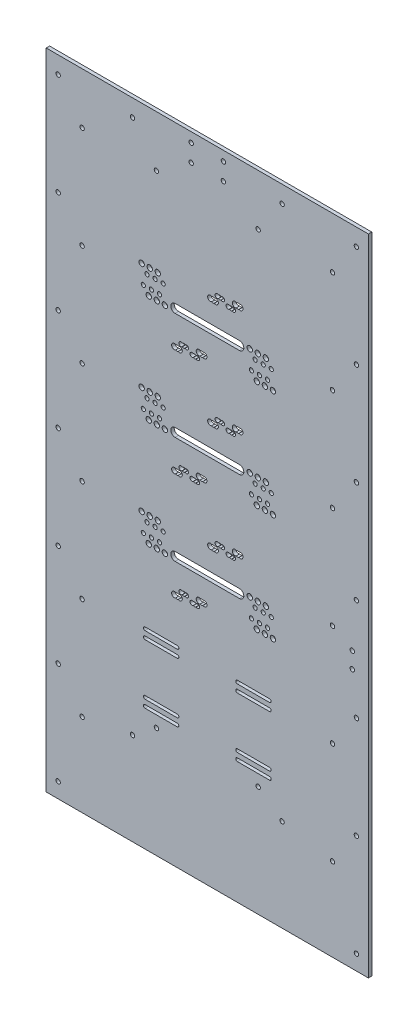
SolidWorks part; units mm, degrees
ref_plane "Front Plane" through (0, 0, 0) normal (0, 0, 1) x (1, 0, 0)
ref_plane "Top Plane" through (0, 0, 0) normal (0, 1, 0) x (1, 0, 0)
ref_plane "Right Plane" through (0, 0, 0) normal (1, 0, 0) x (0, 0, -1)
sketch "Sketch1" plane through (0, 0, 0) normal (0, 0, 1) x (1, 0, 0)
  line L1 (-165.9868, 403.6022) -> (134.0132, 403.6022)
  line L2 (-165.9868, 403.6022) -> (-165.9868, -196.3978)
  line L3 (-165.9868, -196.3978) -> (134.0132, -196.3978)
  line L4 (134.0132, 403.6022) -> (134.0132, -196.3978)
  dimension "D1" = 600
  dimension "D2" = 300
extrude "Boss-Extrude1" add sketch "Sketch1" along normal blind 3.175
sketch "Sketch2" plane through (0, 0, 0) normal (0, 0, -1) x (-1, 0, 0)
  line L0 (15.9868, -196.3978) -> (15.9868, 403.6022) construction
  line L1 (165.9868, -196.3978) -> (-134.0132, -196.3978) construction
  line L2 (-134.0132, 403.6022) -> (165.9868, 403.6022) construction
  line L3 (0.9868, 53.6022) -> (30.9868, 53.6022) construction
  line L4 (0.9868, 153.6022) -> (30.9868, 153.6022) construction
  line L5 (0.9868, 253.6022) -> (30.9868, 253.6022) construction
  point P8 (15.9868, 53.6022)
  point P11 (15.9868, 153.6022)
  dimension "D1" = 30
  dimension "D2" = 30
  dimension "D3" = 100
  dimension "D4" = 100
  dimension "D5" = 250
sketch "Sketch4" plane through (0, 0, 3.175) normal (0, 0, 1) x (1, 0, 0)
  line L0 (-45.9868, 253.6022) -> (14.0132, 253.6022) construction
  line L1 (-45.9868, 257.6022) -> (14.0132, 257.6022)
  line L2 (-45.9868, 249.6022) -> (14.0132, 249.6022)
  line L3 (-15.9868, -196.3978) -> (-15.9868, 403.6022) construction
  line L4 (-0.9868, 253.6022) -> (-30.9868, 253.6022) construction
  line L5 (-45.9868, 153.6022) -> (14.0132, 153.6022) construction
  line L6 (-45.9868, 157.6022) -> (14.0132, 157.6022)
  line L7 (-45.9868, 149.6022) -> (14.0132, 149.6022)
  line L8 (-45.9868, 53.6022) -> (14.0132, 53.6022) construction
  line L9 (-45.9868, 57.6022) -> (14.0132, 57.6022)
  line L10 (-45.9868, 49.6022) -> (14.0132, 49.6022)
  line L11 (-0.9868, 53.6022) -> (-30.9868, 53.6022) construction
  line L12 (-0.9868, 153.6022) -> (-30.9868, 153.6022) construction
  arc A0 (-45.9868, 257.6022) -> (-45.9868, 249.6022) centre (-45.9868, 253.6022) ccw
  arc A1 (14.0132, 249.6022) -> (14.0132, 257.6022) centre (14.0132, 253.6022) ccw
  arc A2 (-45.9868, 157.6022) -> (-45.9868, 149.6022) centre (-45.9868, 153.6022) ccw
  arc A3 (14.0132, 149.6022) -> (14.0132, 157.6022) centre (14.0132, 153.6022) ccw
  arc A4 (-45.9868, 57.6022) -> (-45.9868, 49.6022) centre (-45.9868, 53.6022) ccw
  arc A5 (14.0132, 49.6022) -> (14.0132, 57.6022) centre (14.0132, 53.6022) ccw
  point P2 (-15.9868, 253.6022)
  point P14 (-15.9868, 153.6022)
  point P21 (-15.9868, 53.6022)
  dimension "D1" = 15
  dimension "D2" = 8
  dimension "D3" = 15
  dimension "D4" = 8
  dimension "D5" = 15
  dimension "D6" = 8
extrude "Cut-Extrude1" cut sketch "Sketch4" against normal blind 10
sketch "Sketch5" plane through (0, 0, 0) normal (0, 0, -1) x (-1, 0, 0)
  line L0 (45.9868, 149.6022) -> (-14.0132, 149.6022) construction
  arc A27 (-11.0351, 86.887) -> (-13.5351, 86.887) centre (-12.2851, 84.722) ccw
  circle A34 centre (-30.1263, 32.8202) radius 2.5
  circle A35 centre (-37.6263, 32.8202) radius 2.5
  circle A36 centre (-45.1263, 32.8202) radius 2.5
  arc A37 (20.0603, 26.9076) -> (22.5603, 26.9076) centre (21.3103, 29.0726) ccw
  arc A38 (20.0603, 31.2377) -> (20.0603, 26.9076) centre (18.8103, 29.0726) ccw
  arc A39 (22.5603, 26.9076) -> (22.5603, 31.2377) centre (23.8103, 29.0726) ccw
  arc A40 (26.3551, 25.5434) -> (26.3551, 22.5501) centre (25.1051, 24.0468) ccw
  arc A41 (28.8551, 25.5434) -> (26.3551, 25.5434) centre (27.6051, 24.0468) ccw
  arc A42 (28.8551, 22.5501) -> (28.8551, 25.5434) centre (30.1051, 24.0468) ccw
  arc A43 (39.214, 26.0116) -> (39.214, 29.0049) centre (40.464, 27.5083) ccw
  arc A44 (36.714, 26.0116) -> (39.214, 26.0116) centre (37.964, 27.5083) ccw
  arc A45 (36.714, 29.0049) -> (36.714, 26.0116) centre (35.464, 27.5083) ccw
  arc A46 (43.0088, 24.6475) -> (43.0088, 20.3174) centre (41.7588, 22.4824) ccw
  arc A47 (43.0088, 20.3174) -> (45.5088, 20.3174) centre (44.2588, 22.4824) ccw
  arc A48 (45.5088, 20.3174) -> (45.5088, 24.6475) centre (46.7588, 22.4824) ccw
  circle A49 centre (-32.6024, 39.1166) radius 1.95
  circle A50 centre (-25.1024, 39.1166) radius 1.95
  circle A51 centre (-40.1024, 39.1166) radius 1.95
  circle A52 centre (-36.0672, 49.4744) radius 1.95
  circle A53 centre (-28.5672, 49.4744) radius 1.95
  circle A54 centre (-43.5672, 49.4744) radius 1.95
  circle A55 centre (-38.5434, 55.7708) radius 2.5
  circle A56 centre (-31.0434, 55.7708) radius 2.5
  circle A57 centre (-23.5434, 55.7708) radius 2.5
  arc A58 (-13.5351, 82.5569) -> (-11.0351, 82.5569) centre (-12.2851, 84.722) ccw
  arc A59 (-13.5351, 86.887) -> (-13.5351, 82.5569) centre (-14.7851, 84.722) ccw
  arc A60 (-11.0351, 82.5569) -> (-11.0351, 86.887) centre (-9.7851, 84.722) ccw
  arc A61 (-7.2404, 81.1928) -> (-7.2404, 78.1994) centre (-8.4904, 79.6961) ccw
  arc A62 (-7.2404, 78.1994) -> (-4.7404, 78.1994) centre (-5.9904, 79.6961) ccw
  arc A63 (-4.7404, 78.1994) -> (-4.7404, 81.1928) centre (-3.4904, 79.6961) ccw
  arc A64 (3.1186, 84.6543) -> (3.1186, 81.6609) centre (1.8686, 83.1576) ccw
  arc A65 (3.1186, 81.6609) -> (5.6186, 81.6609) centre (4.3686, 83.1576) ccw
  arc A66 (5.6186, 81.6609) -> (5.6186, 84.6543) centre (6.8686, 83.1576) ccw
  arc A67 (9.4133, 80.2968) -> (9.4133, 75.9667) centre (8.1633, 78.1317) ccw
  arc A68 (9.4133, 75.9667) -> (11.9133, 75.9667) centre (10.6633, 78.1317) ccw
  arc A69 (11.9133, 75.9667) -> (11.9133, 80.2968) centre (13.1633, 78.1317) ccw
  circle A70 centre (62.0999, 74.3842) radius 2.5
  circle A71 centre (69.5999, 74.3842) radius 2.5
  circle A72 centre (77.0999, 74.3842) radius 2.5
  circle A73 centre (57.0761, 68.0878) radius 1.95
  circle A74 centre (64.5761, 68.0878) radius 1.95
  circle A75 centre (72.0761, 68.0878) radius 1.95
  circle A76 centre (60.5409, 57.7299) radius 1.95
  circle A77 centre (68.0409, 57.7299) radius 1.95
  circle A78 centre (75.5409, 57.7299) radius 1.95
  circle A79 centre (70.5171, 51.4336) radius 2.5
  circle A80 centre (63.0171, 51.4336) radius 2.5
  circle A81 centre (55.5171, 51.4336) radius 2.5
  arc A82 (-4.7404, 81.1928) -> (-7.2404, 81.1928) centre (-5.9904, 79.6961) ccw
  arc A83 (5.6186, 84.6543) -> (3.1186, 84.6543) centre (4.3686, 83.1576) ccw
  arc A84 (11.9133, 80.2968) -> (9.4133, 80.2968) centre (10.6633, 78.1317) ccw
  arc A85 (39.214, 29.0049) -> (36.714, 29.0049) centre (37.964, 27.5083) ccw
  arc A86 (45.5088, 24.6475) -> (43.0088, 24.6475) centre (44.2588, 22.4824) ccw
  arc A87 (26.3551, 22.5501) -> (28.8551, 22.5501) centre (27.6051, 24.0468) ccw
  arc A88 (22.5603, 31.2377) -> (20.0603, 31.2377) centre (21.3103, 29.0726) ccw
  arc A89 (-11.0351, 186.887) -> (-13.5351, 186.887) centre (-12.2851, 184.722) ccw
  circle A90 centre (-30.1263, 132.8202) radius 2.5
  circle A91 centre (-37.6263, 132.8202) radius 2.5
  circle A92 centre (-45.1263, 132.8202) radius 2.5
  arc A93 (20.0603, 126.9076) -> (22.5603, 126.9076) centre (21.3103, 129.0726) ccw
  arc A94 (20.0603, 131.2377) -> (20.0603, 126.9076) centre (18.8103, 129.0726) ccw
  arc A95 (22.5603, 126.9076) -> (22.5603, 131.2377) centre (23.8103, 129.0726) ccw
  arc A96 (26.3551, 125.5434) -> (26.3551, 122.5501) centre (25.1051, 124.0468) ccw
  arc A97 (28.8551, 125.5434) -> (26.3551, 125.5434) centre (27.6051, 124.0468) ccw
  arc A98 (28.8551, 122.5501) -> (28.8551, 125.5434) centre (30.1051, 124.0468) ccw
  arc A99 (39.214, 126.0116) -> (39.214, 129.0049) centre (40.464, 127.5083) ccw
  arc A100 (36.714, 126.0116) -> (39.214, 126.0116) centre (37.964, 127.5083) ccw
  arc A101 (36.714, 129.0049) -> (36.714, 126.0116) centre (35.464, 127.5083) ccw
  arc A102 (43.0088, 124.6475) -> (43.0088, 120.3174) centre (41.7588, 122.4824) ccw
  arc A103 (43.0088, 120.3174) -> (45.5088, 120.3174) centre (44.2588, 122.4824) ccw
  arc A104 (45.5088, 120.3174) -> (45.5088, 124.6475) centre (46.7588, 122.4824) ccw
  circle A105 centre (-32.6024, 139.1166) radius 1.95
  circle A106 centre (-25.1024, 139.1166) radius 1.95
  circle A107 centre (-40.1024, 139.1166) radius 1.95
  circle A108 centre (-36.0672, 149.4744) radius 1.95
  circle A109 centre (-28.5672, 149.4744) radius 1.95
  circle A110 centre (-43.5672, 149.4744) radius 1.95
  circle A111 centre (-38.5434, 155.7708) radius 2.5
  circle A112 centre (-31.0434, 155.7708) radius 2.5
  circle A113 centre (-23.5434, 155.7708) radius 2.5
  arc A114 (-13.5351, 182.5569) -> (-11.0351, 182.5569) centre (-12.2851, 184.722) ccw
  arc A115 (-13.5351, 186.887) -> (-13.5351, 182.5569) centre (-14.7851, 184.722) ccw
  arc A116 (-11.0351, 182.5569) -> (-11.0351, 186.887) centre (-9.7851, 184.722) ccw
  arc A117 (-7.2404, 181.1928) -> (-7.2404, 178.1994) centre (-8.4904, 179.6961) ccw
  arc A118 (-7.2404, 178.1994) -> (-4.7404, 178.1994) centre (-5.9904, 179.6961) ccw
  arc A119 (-4.7404, 178.1994) -> (-4.7404, 181.1928) centre (-3.4904, 179.6961) ccw
  arc A120 (3.1186, 184.6543) -> (3.1186, 181.6609) centre (1.8686, 183.1576) ccw
  arc A121 (3.1186, 181.6609) -> (5.6186, 181.6609) centre (4.3686, 183.1576) ccw
  arc A122 (5.6186, 181.6609) -> (5.6186, 184.6543) centre (6.8686, 183.1576) ccw
  arc A123 (9.4133, 180.2968) -> (9.4133, 175.9667) centre (8.1633, 178.1317) ccw
  arc A124 (9.4133, 175.9667) -> (11.9133, 175.9667) centre (10.6633, 178.1317) ccw
  arc A125 (11.9133, 175.9667) -> (11.9133, 180.2968) centre (13.1633, 178.1317) ccw
  circle A126 centre (62.0999, 174.3842) radius 2.5
  circle A127 centre (69.5999, 174.3842) radius 2.5
  circle A128 centre (77.0999, 174.3842) radius 2.5
  circle A129 centre (57.0761, 168.0878) radius 1.95
  circle A130 centre (64.5761, 168.0878) radius 1.95
  circle A131 centre (72.0761, 168.0878) radius 1.95
  circle A132 centre (60.5409, 157.7299) radius 1.95
  circle A133 centre (68.0409, 157.7299) radius 1.95
  circle A134 centre (75.5409, 157.7299) radius 1.95
  circle A135 centre (70.5171, 151.4336) radius 2.5
  circle A136 centre (63.0171, 151.4336) radius 2.5
  circle A137 centre (55.5171, 151.4336) radius 2.5
  arc A138 (-4.7404, 181.1928) -> (-7.2404, 181.1928) centre (-5.9904, 179.6961) ccw
  arc A139 (5.6186, 184.6543) -> (3.1186, 184.6543) centre (4.3686, 183.1576) ccw
  arc A140 (11.9133, 180.2968) -> (9.4133, 180.2968) centre (10.6633, 178.1317) ccw
  arc A141 (39.214, 129.0049) -> (36.714, 129.0049) centre (37.964, 127.5083) ccw
  arc A142 (45.5088, 124.6475) -> (43.0088, 124.6475) centre (44.2588, 122.4824) ccw
  arc A143 (26.3551, 122.5501) -> (28.8551, 122.5501) centre (27.6051, 124.0468) ccw
  arc A144 (22.5603, 131.2377) -> (20.0603, 131.2377) centre (21.3103, 129.0726) ccw
  arc A145 (-11.0351, 286.887) -> (-13.5351, 286.887) centre (-12.2851, 284.722) ccw
  circle A146 centre (-30.1263, 232.8202) radius 2.5
  circle A147 centre (-37.6263, 232.8202) radius 2.5
  circle A148 centre (-45.1263, 232.8202) radius 2.5
  arc A149 (20.0603, 226.9076) -> (22.5603, 226.9076) centre (21.3103, 229.0726) ccw
  arc A150 (20.0603, 231.2377) -> (20.0603, 226.9076) centre (18.8103, 229.0726) ccw
  arc A151 (22.5603, 226.9076) -> (22.5603, 231.2377) centre (23.8103, 229.0726) ccw
  arc A152 (26.3551, 225.5434) -> (26.3551, 222.5501) centre (25.1051, 224.0468) ccw
  arc A153 (28.8551, 225.5434) -> (26.3551, 225.5434) centre (27.6051, 224.0468) ccw
  arc A154 (28.8551, 222.5501) -> (28.8551, 225.5434) centre (30.1051, 224.0468) ccw
  arc A155 (39.214, 226.0116) -> (39.214, 229.0049) centre (40.464, 227.5083) ccw
  arc A156 (36.714, 226.0116) -> (39.214, 226.0116) centre (37.964, 227.5083) ccw
  arc A157 (36.714, 229.0049) -> (36.714, 226.0116) centre (35.464, 227.5083) ccw
  arc A158 (43.0088, 224.6475) -> (43.0088, 220.3174) centre (41.7588, 222.4824) ccw
  arc A159 (43.0088, 220.3174) -> (45.5088, 220.3174) centre (44.2588, 222.4824) ccw
  arc A160 (45.5088, 220.3174) -> (45.5088, 224.6475) centre (46.7588, 222.4824) ccw
  circle A161 centre (-32.6024, 239.1166) radius 1.95
  circle A162 centre (-25.1024, 239.1166) radius 1.95
  circle A163 centre (-40.1024, 239.1166) radius 1.95
  circle A164 centre (-36.0672, 249.4744) radius 1.95
  circle A165 centre (-28.5672, 249.4744) radius 1.95
  circle A166 centre (-43.5672, 249.4744) radius 1.95
  circle A167 centre (-38.5434, 255.7708) radius 2.5
  circle A168 centre (-31.0434, 255.7708) radius 2.5
  circle A169 centre (-23.5434, 255.7708) radius 2.5
  arc A170 (-13.5351, 282.5569) -> (-11.0351, 282.5569) centre (-12.2851, 284.722) ccw
  arc A171 (-13.5351, 286.887) -> (-13.5351, 282.5569) centre (-14.7851, 284.722) ccw
  arc A172 (-11.0351, 282.5569) -> (-11.0351, 286.887) centre (-9.7851, 284.722) ccw
  arc A173 (-7.2404, 281.1928) -> (-7.2404, 278.1994) centre (-8.4904, 279.6961) ccw
  arc A174 (-7.2404, 278.1994) -> (-4.7404, 278.1994) centre (-5.9904, 279.6961) ccw
  arc A175 (-4.7404, 278.1994) -> (-4.7404, 281.1928) centre (-3.4904, 279.6961) ccw
  arc A176 (3.1186, 284.6543) -> (3.1186, 281.6609) centre (1.8686, 283.1576) ccw
  arc A177 (3.1186, 281.6609) -> (5.6186, 281.6609) centre (4.3686, 283.1576) ccw
  arc A178 (5.6186, 281.6609) -> (5.6186, 284.6543) centre (6.8686, 283.1576) ccw
  arc A179 (9.4133, 280.2968) -> (9.4133, 275.9667) centre (8.1633, 278.1317) ccw
  arc A180 (9.4133, 275.9667) -> (11.9133, 275.9667) centre (10.6633, 278.1317) ccw
  arc A181 (11.9133, 275.9667) -> (11.9133, 280.2968) centre (13.1633, 278.1317) ccw
  circle A182 centre (62.0999, 274.3842) radius 2.5
  circle A183 centre (69.5999, 274.3842) radius 2.5
  circle A184 centre (77.0999, 274.3842) radius 2.5
  circle A185 centre (57.0761, 268.0878) radius 1.95
  circle A186 centre (64.5761, 268.0878) radius 1.95
  circle A187 centre (72.0761, 268.0878) radius 1.95
  circle A188 centre (60.5409, 257.7299) radius 1.95
  circle A189 centre (68.0409, 257.7299) radius 1.95
  circle A190 centre (75.5409, 257.7299) radius 1.95
  circle A191 centre (70.5171, 251.4336) radius 2.5
  circle A192 centre (63.0171, 251.4336) radius 2.5
  circle A193 centre (55.5171, 251.4336) radius 2.5
  arc A194 (-4.7404, 281.1928) -> (-7.2404, 281.1928) centre (-5.9904, 279.6961) ccw
  arc A195 (5.6186, 284.6543) -> (3.1186, 284.6543) centre (4.3686, 283.1576) ccw
  arc A196 (11.9133, 280.2968) -> (9.4133, 280.2968) centre (10.6633, 278.1317) ccw
  arc A197 (39.214, 229.0049) -> (36.714, 229.0049) centre (37.964, 227.5083) ccw
  arc A198 (45.5088, 224.6475) -> (43.0088, 224.6475) centre (44.2588, 222.4824) ccw
  arc A199 (26.3551, 222.5501) -> (28.8551, 222.5501) centre (27.6051, 224.0468) ccw
  arc A200 (22.5603, 231.2377) -> (20.0603, 231.2377) centre (21.3103, 229.0726) ccw
  dimension "D1" = 3
extrude "Cut-Extrude4" cut sketch "Sketch5" against normal blind 10
sketch "Sketch6" plane through (0, 0, 0) normal (0, 0, -1) x (-1, 0, 0)
  circle A0 centre (0.9868, 394.6022) radius 2.05
  circle A1 centre (30.9868, 394.6022) radius 2.05
  circle A2 centre (30.9868, 378.6022) radius 2.05
  circle A3 centre (0.9868, 378.6022) radius 2.05
  dimension "D1" = 4.1
extrude "Cut-Extrude5" cut sketch "Sketch6" against normal blind 51
sketch "Sketch7" plane through (0, 0, 0) normal (0, 0, -1) x (-1, 0, 0)
  line L0 (-42.0132, -26.0503) -> (-12.0132, -26.0503) construction
  line L1 (-42.0132, -24.5503) -> (-12.0132, -24.5503)
  line L2 (-42.0132, -27.5503) -> (-12.0132, -27.5503)
  line L3 (-62.0132, -72.5503) -> (-62.0132, -27.5503) construction
  line L6 (-42.0132, -18.7418) -> (-12.0132, -18.7418) construction
  line L7 (-42.0132, -17.2418) -> (-12.0132, -17.2418)
  line L8 (-42.0132, -20.2418) -> (-12.0132, -20.2418)
  line L9 (-59.0132, -24.5503) -> (90.9868, -24.5503) construction
  line L10 (43.9868, -26.0503) -> (73.9868, -26.0503) construction
  line L11 (43.9868, -24.5503) -> (73.9868, -24.5503)
  line L12 (43.9868, -27.5503) -> (73.9868, -27.5503)
  line L13 (43.9868, -18.7418) -> (73.9868, -18.7418) construction
  line L14 (43.9868, -17.2418) -> (73.9868, -17.2418)
  line L15 (43.9868, -20.2418) -> (73.9868, -20.2418)
  line L16 (43.9868, -81.3587) -> (73.9868, -81.3587) construction
  line L17 (43.9868, -79.8587) -> (73.9868, -79.8587)
  line L18 (43.9868, -82.8587) -> (73.9868, -82.8587)
  line L19 (43.9868, -74.0503) -> (73.9868, -74.0503) construction
  line L20 (43.9868, -72.5503) -> (73.9868, -72.5503)
  line L21 (43.9868, -75.5503) -> (73.9868, -75.5503)
  line L22 (-42.0132, -81.3587) -> (-12.0132, -81.3587) construction
  line L23 (-42.0132, -79.8587) -> (-12.0132, -79.8587)
  line L24 (-42.0132, -82.8587) -> (-12.0132, -82.8587)
  line L25 (-42.0132, -74.0503) -> (-12.0132, -74.0503) construction
  line L26 (-42.0132, -72.5503) -> (-12.0132, -72.5503)
  line L27 (-42.0132, -75.5503) -> (-12.0132, -75.5503)
  line L28 (93.9868, -72.5503) -> (93.9868, -27.5503) construction
  line L29 (90.9868, -75.5503) -> (-59.0132, -75.5503) construction
  arc A0 (-42.0132, -24.5503) -> (-42.0132, -27.5503) centre (-42.0132, -26.0503) ccw
  arc A1 (-12.0132, -27.5503) -> (-12.0132, -24.5503) centre (-12.0132, -26.0503) ccw
  arc A4 (-42.0132, -17.2418) -> (-42.0132, -20.2418) centre (-42.0132, -18.7418) ccw
  arc A5 (-12.0132, -20.2418) -> (-12.0132, -17.2418) centre (-12.0132, -18.7418) ccw
  arc A6 (43.9868, -24.5503) -> (43.9868, -27.5503) centre (43.9868, -26.0503) ccw
  arc A7 (73.9868, -27.5503) -> (73.9868, -24.5503) centre (73.9868, -26.0503) ccw
  arc A8 (43.9868, -17.2418) -> (43.9868, -20.2418) centre (43.9868, -18.7418) ccw
  arc A9 (73.9868, -20.2418) -> (73.9868, -17.2418) centre (73.9868, -18.7418) ccw
  arc A10 (43.9868, -79.8587) -> (43.9868, -82.8587) centre (43.9868, -81.3587) ccw
  arc A11 (73.9868, -82.8587) -> (73.9868, -79.8587) centre (73.9868, -81.3587) ccw
  arc A12 (43.9868, -72.5503) -> (43.9868, -75.5503) centre (43.9868, -74.0503) ccw
  arc A13 (73.9868, -75.5503) -> (73.9868, -72.5503) centre (73.9868, -74.0503) ccw
  arc A14 (-42.0132, -79.8587) -> (-42.0132, -82.8587) centre (-42.0132, -81.3587) ccw
  arc A15 (-12.0132, -82.8587) -> (-12.0132, -79.8587) centre (-12.0132, -81.3587) ccw
  arc A16 (-42.0132, -72.5503) -> (-42.0132, -75.5503) centre (-42.0132, -74.0503) ccw
  arc A17 (-12.0132, -75.5503) -> (-12.0132, -72.5503) centre (-12.0132, -74.0503) ccw
  point P2 (-27.0132, -26.0503)
  point P14 (-27.0132, -18.7418)
  point P23 (58.9868, -26.0503)
  point P28 (58.9868, -18.7418)
  point P37 (58.9868, -81.3587)
  point P42 (58.9868, -74.0503)
  point P51 (-27.0132, -81.3587)
  point P56 (-27.0132, -74.0503)
  dimension "D1" = 3
  dimension "D2" = 30
  dimension "D3" = 4.3085
  dimension "D4" = 3
  dimension "D5" = 20
  dimension "D6" = 3
  dimension "D7" = 30
  dimension "D8" = 4.3085
  dimension "D9" = 3
  dimension "D10" = 3
  dimension "D11" = 30
  dimension "D12" = 4.3085
  dimension "D13" = 3
  dimension "D14" = 3
  dimension "D15" = 30
  dimension "D16" = 4.3085
  dimension "D17" = 3
  dimension "D18" = 20
extrude "Cut-Extrude6" cut sketch "Sketch7" against normal blind 51
sketch "Sketch8" plane through (0, 0, 0) normal (0, 0, -1) x (-1, 0, 0)
  circle A0 centre (-119.0132, 60.1072) radius 2.1
  circle A1 centre (-119.0132, 45.1072) radius 2.1
  dimension "D1" = 4.2
extrude "Cut-Extrude7" cut sketch "Sketch8" against normal blind 67
sketch "Sketch9" plane through (0, 0, 0) normal (0, 0, -1) x (-1, 0, 0)
  line L0 (15.9868, 403.6022) -> (15.9868, 432.1874) construction
  line L1 (-134.0132, 403.6022) -> (165.9868, 403.6022) construction
  circle A0 centre (-122.8746, 387.7233) radius 2.05
  circle A1 centre (-100.5974, 355.9656) radius 2.05
  circle A2 centre (-53.6482, 387.7233) radius 2.05
  circle A3 centre (-31.371, 355.9656) radius 2.05
  circle A4 centre (-122.8746, 292.7233) radius 2.05
  circle A5 centre (-100.5974, 260.9656) radius 2.05
  circle A6 centre (-122.8746, 197.7233) radius 2.05
  circle A7 centre (-100.5974, 165.9656) radius 2.05
  circle A8 centre (-122.8746, 102.7233) radius 2.05
  circle A9 centre (-100.5974, 70.9656) radius 2.05
  circle A10 centre (-122.8746, 7.7233) radius 2.05
  circle A11 centre (-100.5974, -24.0344) radius 2.05
  circle A12 centre (-122.8746, -87.2767) radius 2.05
  circle A13 centre (-100.5974, -119.0344) radius 2.05
  circle A14 centre (-122.8746, -182.2767) radius 2.05
  circle A15 centre (-100.5974, -214.0344) radius 2.05
  circle A16 centre (-53.6482, -110.281) radius 2.05
  circle A17 centre (-31.371, -93.4112) radius 2.05
  circle A18 centre (63.3447, -93.4112) radius 2.05
  circle A19 centre (85.6219, -110.281) radius 2.05
  circle A20 centre (132.5711, -214.0344) radius 2.05
  circle A21 centre (154.8483, -182.2767) radius 2.05
  circle A22 centre (132.5711, -119.0344) radius 2.05
  circle A23 centre (154.8483, -87.2767) radius 2.05
  circle A24 centre (132.5711, -24.0344) radius 2.05
  circle A25 centre (154.8483, 7.7233) radius 2.05
  circle A26 centre (132.5711, 70.9656) radius 2.05
  circle A27 centre (154.8483, 102.7233) radius 2.05
  circle A28 centre (132.5711, 165.9656) radius 2.05
  circle A29 centre (154.8483, 197.7233) radius 2.05
  circle A30 centre (132.5711, 260.9656) radius 2.05
  circle A31 centre (154.8483, 292.7233) radius 2.05
  circle A32 centre (63.3447, 355.9656) radius 2.05
  circle A33 centre (85.6219, 387.7233) radius 2.05
  circle A34 centre (132.5711, 355.9656) radius 2.05
  circle A35 centre (154.8483, 387.7233) radius 2.05
  dimension "D1" = 7
extrude "Cut-Extrude8" cut sketch "Sketch9" against normal blind 10
